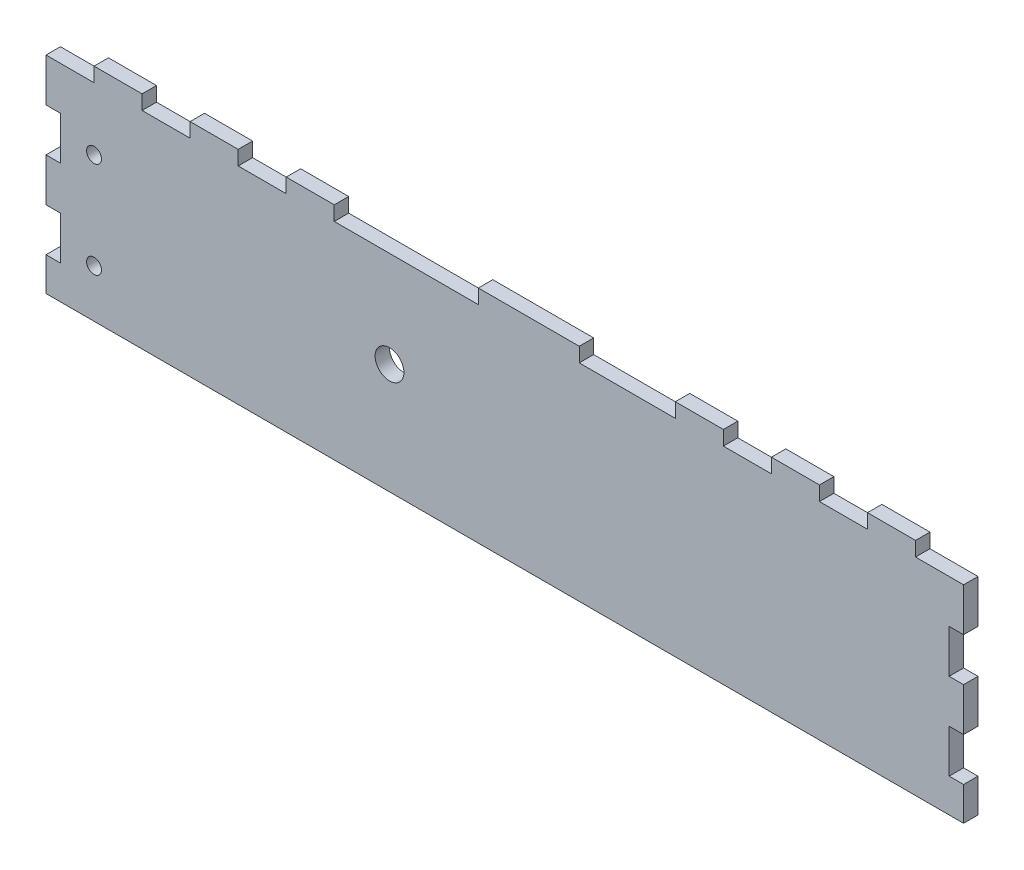
SolidWorks part; units mm, degrees
ref_plane "Front Plane" through (0, 0, 0) normal (0, 0, 1) x (1, 0, 0)
ref_plane "Top Plane" through (0, 0, 0) normal (0, 1, 0) x (1, 0, 0)
ref_plane "Right Plane" through (0, 0, 0) normal (1, 0, 0) x (0, 0, -1)
sketch "Sketch1" plane through (0, 0, 0) normal (0, 0, 1) x (1, 0, 0)
  line L4 (-191, 0) -> (0, 0)
  line L5 (0, 0) -> (0, 46)
  line L6 (0, 46) -> (-191, 46)
  line L7 (-191, 46) -> (-191, 0)
  line L8 (-191, 0) -> (0, 0)
  line L9 (0, 0) -> (0, 46)
  line L10 (0, 46) -> (-191, 46)
  line L11 (-191, 46) -> (-191, 0)
  circle A0 centre (-181, 30) radius 1.55 construction
  circle A1 centre (-181, 10) radius 1.55 construction
  circle A2 centre (-181, 30) radius 1.55
  circle A3 centre (-181, 10) radius 1.55
  dimension "D1" = 0
extrude "Boss-Extrude1" add sketch "Sketch1" along normal blind 3
sketch "Sketch5" plane through (0, 0, 3) normal (0, 0, 1) x (1, 0, 0)
  line L0 (-95.5, 0) -> (-95.5, 46) construction
  line L1 (-191, 0) -> (0, 0) construction
  line L2 (0, 46) -> (-191, 46) construction
ref_axis "Axis1" through (-95.5, 0, 3) along (0, 1, 0)
ref_plane "Plane1" through (-95.5, 0, 0) normal (1, 0, 0) x (0, 1, 0)
sketch "Sketch2" plane through (0, 0, 3) normal (0, 0, 1) x (1, 0, 0)
  line L0 (-119.5, 46) -> (-119.5, 0) construction
  line L1 (-119.5, 46) -> (-119.5, 0)
  point P2 (-119.5, 23)
ref_point "MointPoint-Sus"
sketch "Sketch3" plane through (0, 0, 0) normal (0, 0, -1) x (-1, 0, 0)
  line L4 (50, 43) -> (50, 46)
  line L5 (50, 46) -> (40, 46)
  line L6 (40, 46) -> (40, 43)
  line L7 (40, 43) -> (50, 43)
  line L8 (50, 43) -> (50, 46)
  line L9 (50, 46) -> (40, 46)
  line L10 (40, 46) -> (40, 43)
  line L11 (40, 43) -> (50, 43)
  line L12 (30, 43) -> (30, 46)
  line L13 (30, 46) -> (20, 46)
  line L14 (20, 46) -> (20, 43)
  line L15 (20, 43) -> (30, 43)
  line L16 (30, 43) -> (30, 46)
  line L17 (30, 46) -> (20, 46)
  line L18 (20, 46) -> (20, 43)
  line L19 (20, 43) -> (30, 43)
  line L20 (10, 43) -> (10, 46)
  line L21 (10, 46) -> (0, 46)
  line L22 (0, 46) -> (0, 43)
  line L23 (0, 43) -> (10, 43)
  line L24 (10, 43) -> (10, 46)
  line L25 (10, 46) -> (0, 46)
  line L26 (0, 46) -> (0, 43)
  line L27 (0, 43) -> (10, 43)
  line L28 (171, 43) -> (171, 46)
  line L29 (171, 46) -> (161, 46)
  line L30 (161, 46) -> (161, 43)
  line L31 (161, 43) -> (171, 43)
  line L32 (171, 43) -> (171, 46)
  line L33 (171, 46) -> (161, 46)
  line L34 (161, 46) -> (161, 43)
  line L35 (161, 43) -> (171, 43)
  line L36 (151, 43) -> (151, 46)
  line L37 (151, 46) -> (141, 46)
  line L38 (141, 46) -> (141, 43)
  line L39 (141, 43) -> (151, 43)
  line L40 (151, 43) -> (151, 46)
  line L41 (151, 46) -> (141, 46)
  line L42 (141, 46) -> (141, 43)
  line L43 (141, 43) -> (151, 43)
  line L44 (131, 46) -> (101, 46)
  line L45 (101, 46) -> (101, 43)
  line L46 (101, 43) -> (131, 43)
  line L47 (131, 43) -> (131, 46)
  line L48 (131, 46) -> (101, 46)
  line L49 (101, 46) -> (101, 43)
  line L50 (101, 43) -> (131, 43)
  line L51 (131, 43) -> (131, 46)
  line L52 (80, 46) -> (60, 46)
  line L53 (80, 43) -> (80, 46)
  line L54 (60, 43) -> (80, 43)
  line L55 (60, 46) -> (60, 43)
  line L56 (80, 46) -> (60, 46)
  line L57 (80, 43) -> (80, 46)
  line L58 (60, 43) -> (80, 43)
  line L59 (60, 46) -> (60, 43)
  line L60 (181, 43) -> (191, 43)
  line L61 (181, 46) -> (181, 43)
  line L62 (191, 46) -> (181, 46)
  line L63 (191, 43) -> (191, 46)
  line L64 (181, 43) -> (191, 43)
  line L65 (181, 46) -> (181, 43)
  line L66 (191, 46) -> (181, 46)
  line L67 (191, 43) -> (191, 46)
  dimension "D1" = 0
  dimension "D2" = 0
  dimension "D3" = 0
  dimension "D4" = 0
  dimension "D5" = 0
  dimension "D6" = 0
  dimension "D7" = 0
  dimension "D8" = 0
extrude "Cut-Extrude1" cut sketch "Sketch3" against normal up to next
sketch "Sketch4" plane through (0, 0, 3) normal (0, 0, 1) x (1, 0, 0)
  line L0 (-3, 43) -> (-3, 0) construction
  line L1 (0, 43) -> (-10, 43) construction
  line L2 (-191, 0) -> (0, 0) construction
  line L3 (0, 0) -> (0, 43) construction
  line L4 (-3, 34) -> (0, 34)
  line L5 (-3, 25) -> (0, 25)
  line L6 (-3, 16) -> (0, 16)
  line L7 (-3, 7) -> (0, 7)
  line L8 (0, 34) -> (0, 25)
  line L9 (-3, 25) -> (-3, 34)
  line L10 (0, 16) -> (0, 7)
  line L11 (-3, 7) -> (-3, 16)
  dimension "D1" = 3
  dimension "D2" = 9
  dimension "D3" = 4
extrude "Cut-Extrude2" cut sketch "Sketch4" against normal up to next
mirror "Mirror1" about plane through (-95.5, 0, 0) normal (1, 0, 0) of "Cut-Extrude2"
sketch "Sketch6" plane through (0, 0, 3) normal (0, 0, 1) x (1, 0, 0)
  circle A0 centre (-119.5, 23) radius 3
  point P0 (-119.5, 23)
  dimension "D1" = 6
extrude "Cut-Extrude3" cut sketch "Sketch6" against normal up to next
